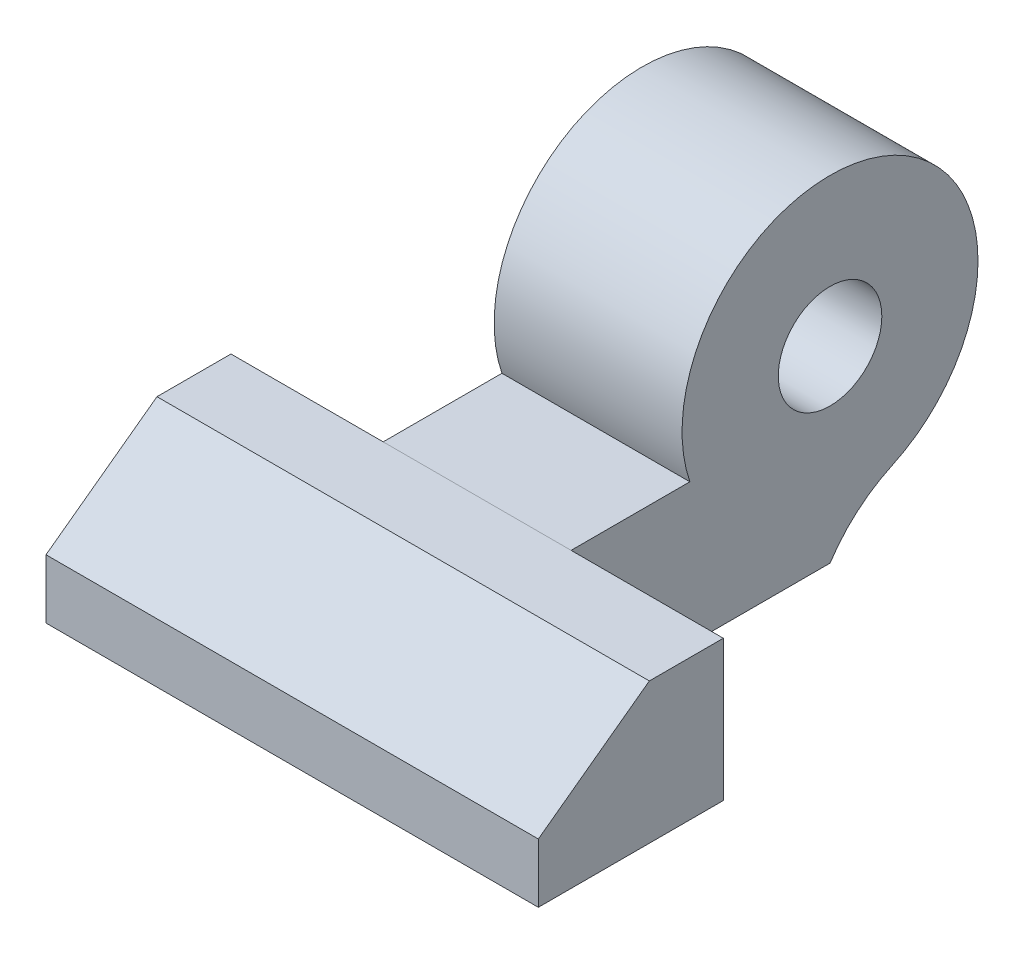
SolidWorks part; units mm, degrees
ref_plane "Front Plane" through (0, 0, 0) normal (0, 0, 1) x (1, 0, 0)
ref_plane "Top Plane" through (0, 0, 0) normal (0, 1, 0) x (1, 0, 0)
ref_plane "Right Plane" through (0, 0, 0) normal (1, 0, 0) x (0, 0, -1)
sketch "Sketch1" plane through (0, 0, 0) normal (1, 0, 0) x (0, 0, -1)
  line L0 (0, -12.7) -> (-30, -12.7)
  line L1 (-30, -12.7) -> (-30, -8.7)
  line L2 (-30, -8.7) -> (-22.5, -3.2)
  line L3 (-22.5, -3.2) -> (-9.4742, -3.2)
  line L5 (0, -12.7) -> (0, -10)
  arc A0 (0, -9.525) -> (-8.9714, -3.2) centre (0, 0) ccw construction
  arc A1 (0, -11) -> (-10.5243, -3.2) centre (0, 0) ccw construction
  circle A2 centre (0, 0) radius 3.5
  arc A3 (0, -10) -> (-9.4742, -3.2) centre (0, 0) ccw
  dimension "D1" = 19.05
  dimension "D2" = 6.5
  dimension "D6" = 22
  dimension "D9" = 7
  dimension "D3" = 9.5
  dimension "D4" = 4
  dimension "D5" = 12.7
  dimension "D7" = 7.5
  dimension "D8" = 30
extrude "Boss-Extrude1" add sketch "Sketch1" along normal mid plane 12.7
sketch "Sketch4" plane through (0, 0, 0) normal (1, 0, 0) x (0, 0, -1)
  line L0 (-17.5, -3.2) -> (-17.5, -12.7)
  line L5 (0, -12.7) -> (0, -10)
  line L6 (-9.4742, -3.2) -> (-22.5, -3.2)
  line L7 (-22.5, -3.2) -> (-30, -8.7)
  line L8 (-30, -8.7) -> (-30, -12.7)
  line L9 (-30, -12.7) -> (0, -12.7)
  line L11 (-17.5, -3.2) -> (-22.5, -3.2)
  line L12 (-22.5, -3.2) -> (-30, -8.7)
  line L13 (-30, -8.7) -> (-30, -12.7)
  line L14 (-30, -12.7) -> (-17.5, -12.7)
  arc A1 (0, -10) -> (-9.4742, -3.2) centre (0, 0) ccw
  dimension "D2" = 5
  dimension "D1" = 0
extrude "Boss-Extrude2" add sketch "Sketch4" along normal mid plane 33.274 separate body contours L11 L12 L13 L14 region at (0, -8.5631, 22.9618)
fillet "Fillet1" radius 10 1 edges at (0, -10, 0)
